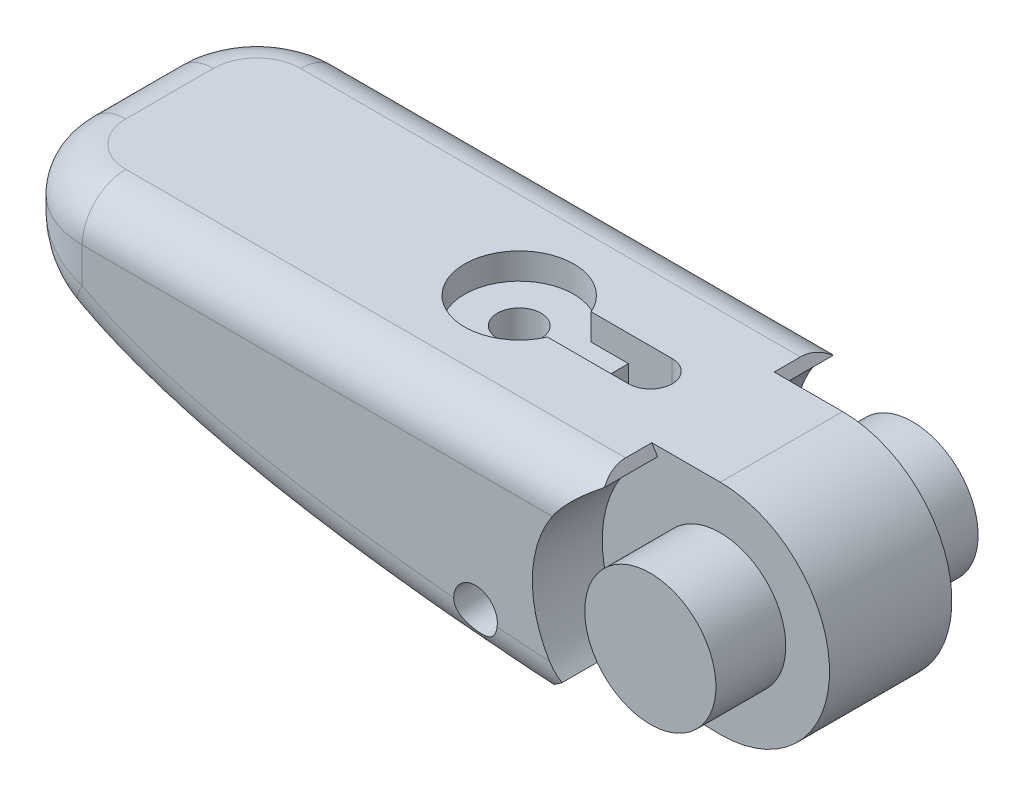
SolidWorks part; units mm, degrees
ref_plane "Front Plane" through (0, 0, 0) normal (0, 0, 1) x (1, 0, 0)
ref_plane "Top Plane" through (0, 0, 0) normal (0, 1, 0) x (1, 0, 0)
ref_plane "Right Plane" through (0, 0, 0) normal (1, 0, 0) x (0, 0, -1)
sketch "Width-Sketch" plane through (0, 0, 0) normal (0, 1, 0) x (1, 0, 0)
  line L0 (0, 0) -> (0, -2) construction
  line L1 (0, -2) -> (0, -4) construction
  line L2 (0, -4) -> (0, -6) construction
  line L3 (0, -6) -> (0, -8) construction
  line L4 (0, -8) -> (0, -10) construction
  dimension "D1" = 2
ref_plane "Centre-Plane" through (0, 0, 6) normal (0, 0, 1) x (1, 0, 0)
sketch "Sketch1" plane through (0, 0, 0) normal (0, 0, 1) x (1, 0, 0)
  line L0 (0, 5) -> (-30, 5)
  arc A2 (0, -5) -> (0, 5) centre (0, 0) ccw
  spline S0 degree 3 poles (-30, 5) (-32.8378, -4.4787) (-0.5767, -5.0045) (0, -5) knots 0 0 0 0 1 1 1 1
  dimension "D1" = 5
  dimension "D2" = 30
extrude "Boss-Extrude1" add sketch "Sketch1" along normal up to vertex (6 mm away) up to point (0, 0, 6)
surface "Surface-Offset1" parameters "D1"=0
sketch "Sketch15" plane through (0, 0, 0) normal (0, 0, -1) x (-1, 0, 0)
  line L0 (2.8667, 4.5763) -> (3.1321, 5)
  line L1 (0, 5) -> (30, 5) construction
  line L2 (3.1321, 5) -> (0.78, 5.3434)
  line L3 (5.6745, -4.7497) -> (4.1409, -3.466)
  line L4 (5.6745, -4.7497) -> (0.6519, -5.3605)
  arc A0 (4.1409, -3.466) -> (2.8667, 4.5763) centre (0, 0) ccw
  arc A1 (0, 5) -> (0, -5) centre (0, 0) ccw construction
  circle A2 centre (0, 0) radius 3
  arc A3 (0.78, 5.3434) -> (0.6519, -5.3605) centre (0, 0) ccw
  spline S0 degree 3 poles (30, 5) (32.8378, -4.4787) (0.5767, -5.0045) (0, -5) knots 0 0 0 0 1 1 1 1 construction
  dimension "D2" = 6
  dimension "D1" = 0.4
  dimension "D3" = 0.5
  dimension "D4" = 2
extrude "Cut-Extrude5" cut sketch "Sketch15" against normal blind 3.2
sketch "Sketch16" plane through (0, 0, 6) normal (0, 0, -1) x (-1, 0, 0)
  line L0 (7, 0) -> (5, 0)
  line L2 (7, 0) -> (7, -7)
  line L4 (0, -5) -> (0, -7)
  line L5 (0, -7) -> (7, -7)
  arc A1 (0, -5) -> (5, 0) centre (0, 0) ccw
  arc A2 (0, 5) -> (0, -5) centre (0, 0) ccw construction
  dimension "D1" = 2
  dimension "D2" = 2
extrude "Cut-Extrude6" cut sketch "Sketch16" along normal blind 1
sketch "Sketch17" plane through (0, 5, 0) normal (0, 1, 0) x (1, 0, 0)
  line L0 (0, -6) -> (-30, -6) construction
  line L1 (-7, -6) -> (-5, -6) construction
  line L2 (-7, -6) -> (-5, -6) construction
  line L3 (0, -6) -> (-30, -6) construction
  circle A0 centre (-6, -6) radius 1
  point P10 (-6, -6)
  dimension "D1" = 2
extrude "Cut-Extrude7" cut sketch "Sketch17" against normal through all
mirror "Mirror1" about plane through (0, 0, 6) normal (0, 0, 1) of bodies 117 111
sketch "Sketch18" plane through (0, 5, 0) normal (0, 1, 0) x (1, 0, 0)
  line L0 (-6, -5) -> (-9.7087, -5)
  line L1 (-6, -5) -> (-12, -5) construction
  line L2 (-6, -5) -> (-6, -7)
  line L3 (-6, -7) -> (-12, -7) construction
  line L4 (-12, -5) -> (-12, -7) construction
  line L6 (-9.7087, -7) -> (-6, -7)
  circle A0 centre (-6, -6) radius 1 construction
  circle A1 centre (-6, -6) radius 1 construction
  arc A2 (-9.7087, -5) -> (-9.7087, -7) centre (-12, -6) ccw
  dimension "D1" = 2.5
  dimension "D2" = 6
extrude "Cut-Extrude8" cut sketch "Sketch18" against normal blind 1.2
sketch "Sketch19" plane through (0, 3.8, 0) normal (0, 1, 0) x (1, 0, 0)
  circle A0 centre (-12, -6) radius 1
  arc A1 (-9.7087, -5) -> (-9.7087, -7) centre (-12, -6) ccw construction
  dimension "D1" = 2
extrude "Cut-Extrude9" cut sketch "Sketch19" against normal through all
sketch "Sketch20" plane through (0, 0, 6) normal (0, 0, 1) x (1, 0, 0)
  line L0 (-11, 3.8) -> (-13, 3.8) construction
  line L1 (-11, 3.8) -> (-13, 3.8) construction
  line L2 (-11, 3.8) -> (-11, -4.2826) construction
  line L3 (-13, 3.8) -> (-13, -4.0432) construction
  line L4 (-12, -6.9171) -> (-10.5, -6.9171)
  line L5 (-10.5, -6.9171) -> (-10.5, -1.6885)
  line L6 (-10.5, 2.2) -> (-12, 2.2)
  line L8 (-12, 3.8) -> (-12, -6.9171) construction
  line L9 (-12, -6.9171) -> (-12, 2.2)
  line L10 (-13, -4.0432) -> (-11, -4.0432) construction
  line L11 (-10.5, -3.977) -> (-13.5, -3.977) construction
  line L12 (-10.5, -0.0885) -> (-8.5, -0.0885)
  line L13 (-8.5, -0.0885) -> (-8.5, -1.6885)
  line L14 (-8.5, -1.6885) -> (-10.5, -1.6885)
  line L15 (-10.5, -0.0885) -> (-10.5, 2.2)
  line L16 (-11.3066, -3.977) -> (-11.3066, 2.2) construction
  line L17 (-8.5, -0.8885) -> (-11.3066, -0.8885) construction
  line L18 (-9.7087, 3.8) -> (-14.5, 3.8) construction
  spline S0 degree 3 poles (942.7716, 236.742) (-1140.6632, -164.2238) (1122.142, 99.5677) (-1003.311, -73.4499) knots -2.000237 -2.000237 -2.000237 -2.000237 3.075783 3.075783 3.075783 3.075783 only from (-30, 5) to (-5.6745, -4.7497) construction
  spline S1 degree 3 poles (-30, 5) (-32.102, -2.021) (-14.9464, -4.13) (-5.6745, -4.7497) knots 0 0 0 0 0.740721 0.740721 0.740721 0.740721 construction
  point P15 (-12, -3.977)
  dimension "D1" = 1.5
  dimension "D2" = 1.6
  dimension "D3" = 1.6
  dimension "D4" = 2
revolve "Cut-Revolve2" cut sketch "Sketch20" angle 360 about L9
sketch "Sketch21" plane through (0, -0.0885, 0) normal (0, -1, 0) x (1, 0, 0)
  line L0 (-7, 7) -> (-6, 7) construction
  line L1 (-8.6459, 7) -> (-6, 7)
  line L2 (-7, 5) -> (-6, 5) construction
  line L3 (-8.6459, 5) -> (-6, 5)
  line L4 (-6, 7) -> (-6, 5)
  circle A1 centre (-12, 6) radius 3.5
  arc A2 (-8.6459, 5) -> (-8.6459, 7) centre (-12, 6) ccw
  dimension "D1" = 0
extrude "Cut-Extrude10" cut sketch "Sketch21" along normal up to surface (1.6 mm away) up to face at (-12, -1.6885, 2.5)
sketch "Sketch22" plane through (0, 3.8, 0) normal (0, 1, 0) x (1, 0, 0)
  line L0 (-6, -5) -> (-9.7087, -5) construction
  line L1 (-8, -5) -> (-6, -5)
  line L2 (-8, -5) -> (-8, -7)
  line L3 (-8, -7) -> (-6, -7)
  line L4 (-6, -5) -> (-6, -7)
  line L5 (-7, -7) -> (-7, -5) construction
  line L6 (-7, -7) -> (-7, -5) construction
  dimension "D1" = 1
extrude "Cut-Extrude11" cut sketch "Sketch22" against normal through all both and the other way through all
sketch "Sketch23" plane through (0, 0, 5) normal (0, 0, 1) x (1, 0, 0)
  line L0 (-8, -4.5738) -> (-8, -1.6885) construction
  line L1 (-8, -2.4885) -> (-8, -1.6885) construction
  line L2 (-8, -1.6885) -> (-7.2, -1.6885) construction
  line L3 (-8, -4.5738) -> (-8, -1.6885) construction
  line L9 (-7.2, -1.6885) -> (-7.2, -2.4885) construction
  line L10 (-7.2, -2.4885) -> (-8, -2.4885) construction
  circle A0 centre (-8, -2.4885) radius 1
  dimension "D1" = 2
  dimension "D2" = 0.8
extrude "Cut-Extrude12" cut sketch "Sketch23" against normal through all both and the other way through all
sketch "Sketch24" plane through (0, 5, 0) normal (0, 1, 0) x (1, 0, 0)
  line L0 (-30, -8) -> (-30, -4)
  line L1 (-26, -12) -> (-38, -12)
  line L2 (-38, -12) -> (-38, 0)
  line L3 (-38, 0) -> (-26, 0)
  line L4 (-30, -12) -> (-30, 0) construction
  line L5 (-3.1321, 0) -> (-30, 0) construction
  line L6 (-3.1321, -12) -> (-30, -12) construction
  arc A0 (-30, -4) -> (-26, 0) centre (-26, -4) cw
  arc A1 (-30, -8) -> (-26, -12) centre (-26, -8) ccw
  dimension "D2" = 4
extrude "Cut-Extrude13" cut sketch "Sketch24" against normal through all
fillet "Fillet1" radius 2 10 edges at (-14.566, 5, 0) (-28.8284, 5, 1.1716) (-30, 5, 6) (-28.8284, 5, 10.8284) (-14.566, 5, 12) (-29.5775, 1.8916, 9.7893) (-30, 2.7602, 6) (-29.0648, 1.2347, 1.4296)
equation "\"Ligament\"= 2"
equation "\"D1@Width-Sketch\" = \"Ligament\""
equation "\"Clearance\"=0.4"
equation "\"D1@Sketch15\"=\"Clearance\""
equation "\"D1@Sketch17\"=\"Ligament\""
equation "\"D1@Sketch16\"=\"Ligament\""
equation "\"D1@Cut-Extrude6\"=\"Ligament\"/2"
equation "\"D1@Cut-Extrude8\"=\"Ligament\"/2"
equation "\"Trim\"=0.5"
equation "\"D3@Sketch15\"=\"Trim\""
equation "\"D4@Sketch15\"=\"Trim\"*4"
equation "\"D2@Sketch23\"=\"Clearance\"*2"
